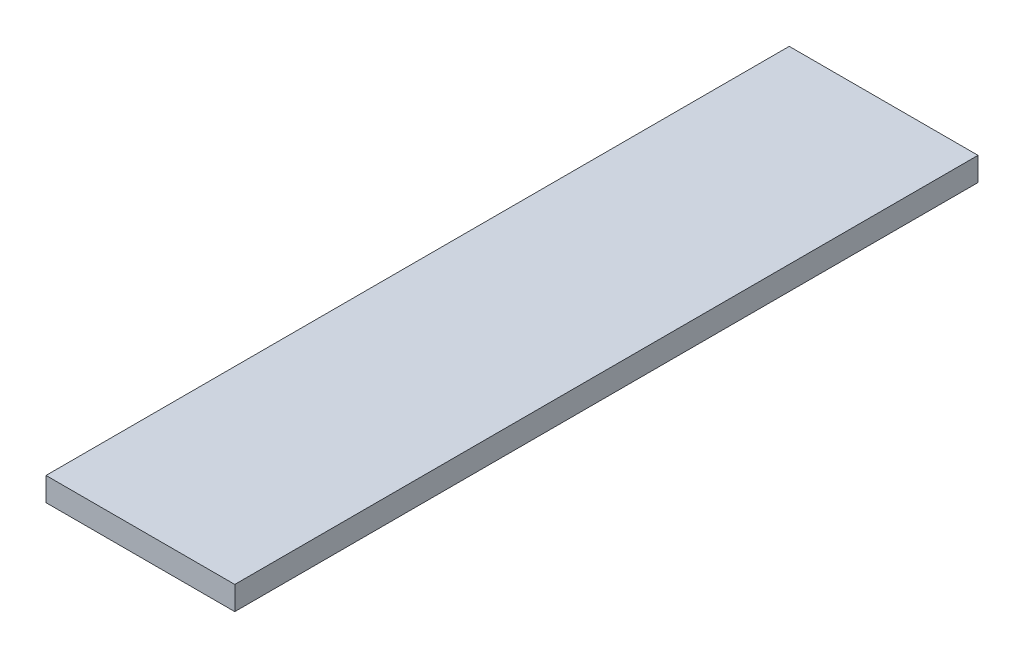
SolidWorks part; units mm, degrees
ref_plane "Front Plane" through (0, 0, 0) normal (0, 0, 1) x (1, 0, 0)
ref_plane "Top Plane" through (0, 0, 0) normal (0, 1, 0) x (1, 0, 0)
ref_plane "Right Plane" through (0, 0, 0) normal (1, 0, 0) x (0, 0, -1)
sketch "Sketch1" plane through (0, 0, 0) normal (0, 1, 0) x (1, 0, 0)
  line L1 (0, 0) -> (25.4, 0)
  line L2 (0, 0) -> (0, 100)
  line L3 (0, 100) -> (25.4, 100)
  line L4 (25.4, 0) -> (25.4, 100)
  dimension "D1" = 100
  dimension "D2" = 25.4
extrude "Boss-Extrude1" add sketch "Sketch1" along normal blind 3.175
